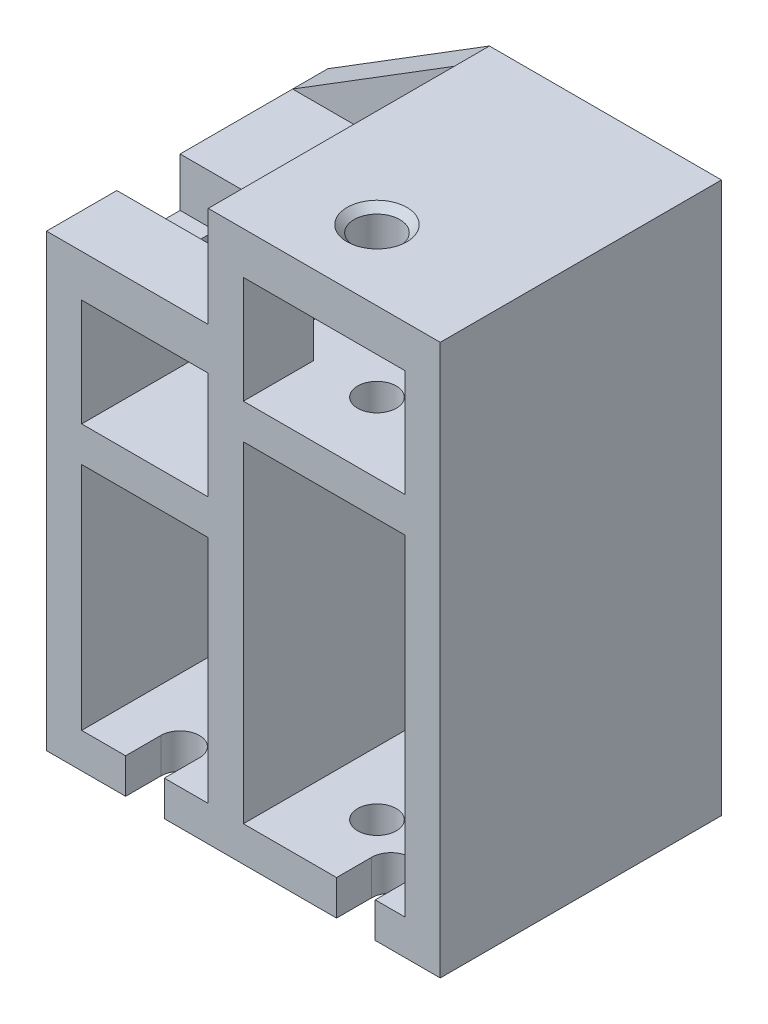
SolidWorks part; units mm, degrees
material "PET"
ref_plane "Front Plane" through (0, 0, 0) normal (0, 0, 1) x (1, 0, 0)
ref_plane "Top Plane" through (0, 0, 0) normal (0, 1, 0) x (1, 0, 0)
ref_plane "Right Plane" through (0, 0, 0) normal (1, 0, 0) x (0, 0, -1)
sketch "Sketch1" plane through (0, 0, 0) normal (0, 0, 1) x (1, 0, 0)
  line L0 (0, 0) -> (0, 64)
  line L1 (23, 78.3) -> (56, 78.3)
  line L2 (56, 78.3) -> (56, 0)
  line L4 (5, 5) -> (5, 37.75)
  line L6 (51, 72.3) -> (51, 57.05)
  line L7 (0, 64) -> (23, 64)
  line L9 (23, 58) -> (5, 58)
  line L10 (5, 42.75) -> (23, 42.75)
  line L11 (5, 5) -> (23, 5)
  line L12 (23, 37.75) -> (5, 37.75)
  line L13 (51, 57.05) -> (28, 57.05)
  line L14 (5, 42.75) -> (5, 58)
  line L15 (28, 52.05) -> (51, 52.05)
  line L18 (51, 52.05) -> (51, 5)
  line L20 (23, 64) -> (23, 58) construction
  line L21 (28, 57.05) -> (28, 72.3)
  line L22 (23, 64) -> (23, 78.3)
  line L23 (28, 72.3) -> (51, 72.3)
  line L24 (28, 52.05) -> (28, 5)
  line L25 (23, 58) -> (23, 42.75)
  line L27 (56, 0) -> (0, 0)
  line L28 (23, 37.75) -> (23, 5)
  line L29 (28, 5) -> (51, 5)
  point P20 (14, 42.75)
  point P22 (37, 57.05)
  dimension "D2" = 5
  dimension "D3" = 5
  dimension "D4" = 6
  dimension "D5" = 15.25
  dimension "D6" = 5
  dimension "D7" = 42.75
  dimension "D8" = 15.25
  dimension "D9" = 23
  dimension "D10" = 5
  dimension "D11" = 5
  dimension "D12" = 23
  dimension "D13" = 18
  dimension "D14" = 5
  dimension "D15" = 6
  dimension "D16" = 57.05
  dimension "D19" = 9
extrude "Boss-Extrude1" add sketch "Sketch1" along normal blind 40 contours L22 L7 L0 L4 L12 L10 L14 L9 L15 L18 L2 L1 L21 L23 L6 L13 region at (0.9626, 32, 0)
sketch "Sketch2" plane through (0, 78.3, 0) normal (0, 1, 0) x (1, 0, 0)
  line L0 (23, -40) -> (56, -40) construction
  line L1 (56, -40) -> (56, 0) construction
  line L3 (0, 0) -> (23, 0) construction
  circle A0 centre (14, -15) radius 2.75
  circle A1 centre (37, -30) radius 2.75
  dimension "D1" = 23
  dimension "D2" = 5.5
  dimension "D3" = 5.5
  dimension "D4" = 19
  dimension "D5" = 10
  dimension "D6" = 15
extrude "Cut-Extrude1" cut sketch "Sketch2" against normal up to surface (40.55 mm away) up to face at (14, 37.75, 20)
sketch "Sketch3" plane through (28, 0, 0) normal (1, 0, 0) x (0, 0, -1)
  line L1 (-21, 72.3) -> (-30, 72.3)
  line L2 (-21, 72.3) -> (-21, 57.05)
  line L3 (-21, 57.05) -> (-30, 57.05)
  line L4 (-30, 72.3) -> (-30, 57.05)
  line L5 (0, 78.3) -> (0, 0) construction
  line L6 (-40, 72.3) -> (0, 72.3) construction
  dimension "D2" = 21
  dimension "D3" = 15.25
  dimension "D4" = 9
extrude "Cut-Extrude2" cut sketch "Sketch3" against normal up to next
sketch "Sketch4" plane through (5, 0, 0) normal (1, 0, 0) x (0, 0, -1)
  line L2 (-5, 42.75) -> (-5, 58)
  line L3 (-5, 58) -> (-15, 58)
  line L4 (-15, 42.75) -> (-15, 58)
  line L5 (0, 78.3) -> (0, 0) construction
  line L6 (-5, 42.75) -> (-15, 42.75)
  line L7 (-40, 42.75) -> (0, 42.75) construction
  dimension "D1" = 5
  dimension "D2" = 10
  dimension "D3" = 15.25
extrude "Cut-Extrude3" cut sketch "Sketch4" against normal through all
sketch "Sketch6" plane through (0, 78.3, 0) normal (0, 1, 0) x (1, 0, 0)
  circle A0 centre (14, -15) radius 3.25
  circle A1 centre (37, -30) radius 3.25
  dimension "D1" = 6.5
  dimension "D2" = 6.5
extrude "Cut-Extrude4" cut sketch "Sketch6" against normal up to next
ref_axis "Axis1" through (37, 72.3, 30) along (0, 1, 0)
ref_plane "Plane1" through (37, 0, 0) normal (1, 0, 0) x (0, 0, -1)
chamfer "Chamfer1" distance 1 angle 45 2 edges at (37, 78.3, 33.25) (14, 64, 18.25)
sketch "Sketch7" plane through (0, 0, 0) normal (0, -1, 0) x (1, 0, 0)
  line L0 (14, 40) -> (14, 0) construction
  line L1 (56, 40) -> (0, 40) construction
  line L2 (56, 0) -> (0, 0) construction
  line L3 (44, 40) -> (44, 0) construction
  line L5 (0, 40) -> (0, 0) construction
  line L7 (0, 15) -> (56, 15) construction
  line L8 (0, 35) -> (56, 35) construction
  line L9 (56, 40) -> (56, 0) construction
  line L10 (11.25, 35) -> (11.25, 40)
  line L11 (56, 40) -> (0, 40) construction
  line L12 (16.75, 35) -> (16.75, 40)
  line L13 (16.75, 40) -> (11.25, 40)
  line L14 (41.25, 35) -> (41.25, 40)
  line L15 (46.75, 35) -> (46.75, 40)
  line L16 (46.75, 40) -> (41.25, 40)
  arc A0 (11.25, 35) -> (16.75, 35) centre (14, 35) ccw
  arc A1 (41.25, 35) -> (46.75, 35) centre (44, 35) ccw
  circle A2 centre (14, 15) radius 3.3
  circle A3 centre (44, 15) radius 3.3
  dimension "D5" = 5.5
  dimension "D6" = 6.6
  dimension "D7" = 5.5
  dimension "D8" = 6.6
  dimension "D1" = 14
  dimension "D2" = 12
  dimension "D3" = 15
  dimension "D4" = 5
extrude "Cut-Extrude5" cut sketch "Sketch7" against normal up to next
sketch "Sketch8" plane through (0, 5, 0) normal (0, 1, 0) x (1, 0, 0)
  circle A0 centre (37, -30) radius 2.75
  dimension "D1" = 5.5
extrude "Cut-Extrude6" cut sketch "Sketch8" against normal through all
sketch "Sketch9" plane through (0, 0, 0) normal (0, 0, -1) x (-1, 0, 0)
  line L0 (-23, 78.3) -> (0, 64)
  line L1 (0, 64) -> (-23, 64)
  line L2 (-23, 64) -> (-23, 78.3)
  line L7 (-51, 52.05) -> (-28, 52.05)
  line L8 (-28, 52.05) -> (-28, 27.05)
  line L9 (-28, 52.05) -> (-28, 5) construction
  line L10 (-5, 5) -> (-5, 37.75) construction
  line L11 (-51, 52.05) -> (-28, 52.05)
  line L12 (-51, 52.05) -> (-51, 27.05)
  line L13 (-51, 27.05) -> (-28, 27.05)
  line L14 (-28, 52.05) -> (-28, 27.05)
  line L15 (-23, 37.75) -> (-5, 37.75)
  line L16 (-23, 37.75) -> (-23, 27.05)
  line L17 (-23, 27.05) -> (-5, 27.05)
  line L18 (-5, 37.75) -> (-5, 27.05)
  dimension "D1" = 25
  dimension "D2" = 25
extrude "Boss-Extrude2" add sketch "Sketch9" against normal up to surface (5 mm away) contours L12 L11 L14 L13 | L16 L15 L18 L17 | L2 L0 L1 up to face at (2.5, 50.375, 5)
